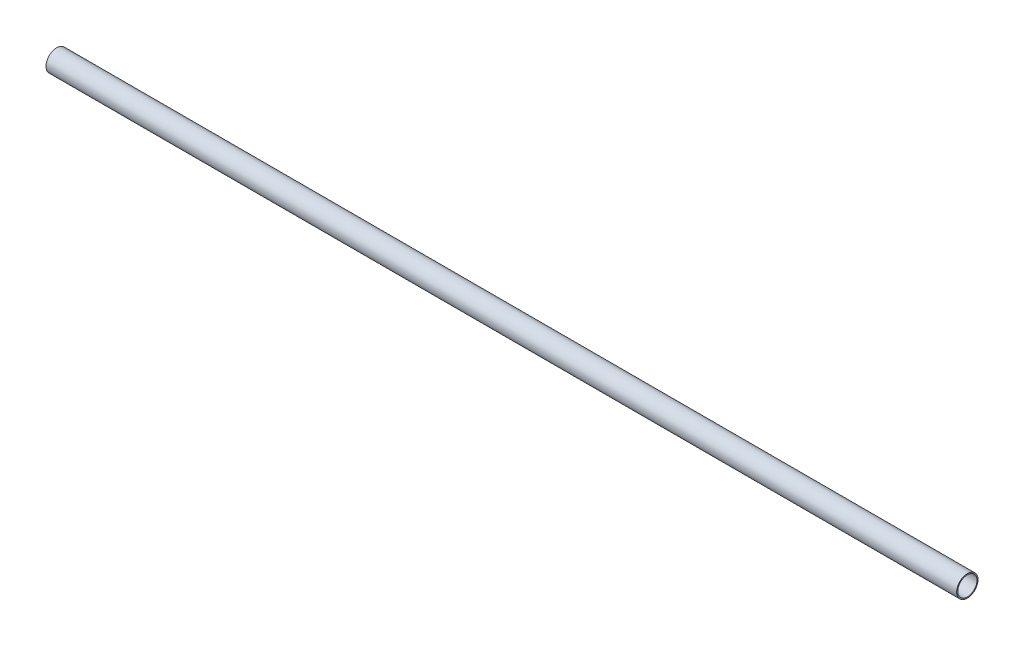
SolidWorks part; units mm, degrees
ref_plane "Front Plane" through (0, 0, 0) normal (0, 0, 1) x (1, 0, 0)
ref_plane "Top Plane" through (0, 0, 0) normal (0, 1, 0) x (1, 0, 0)
ref_plane "Right Plane" through (0, 0, 0) normal (1, 0, 0) x (0, 0, -1)
sketch "Leg_Tube Sketch" plane through (0, 0, 0) normal (0, 0, 1) x (1, 0, 0)
  line L0 (-3000, 0) -> (3000, 0) construction
  line L1 (20, 13.5) -> (1300, 13.5)
  line L2 (1300, 13.5) -> (1300, 15)
  line L3 (1300, 15) -> (20, 15)
  line L4 (20, 15) -> (20, 13.5)
revolve "Leg_Tube" add sketch "Leg_Tube Sketch" angle 360 about L0
ref_axis "Engine Axis" through (1364, 0, 0) along (-1, 0, 0)
